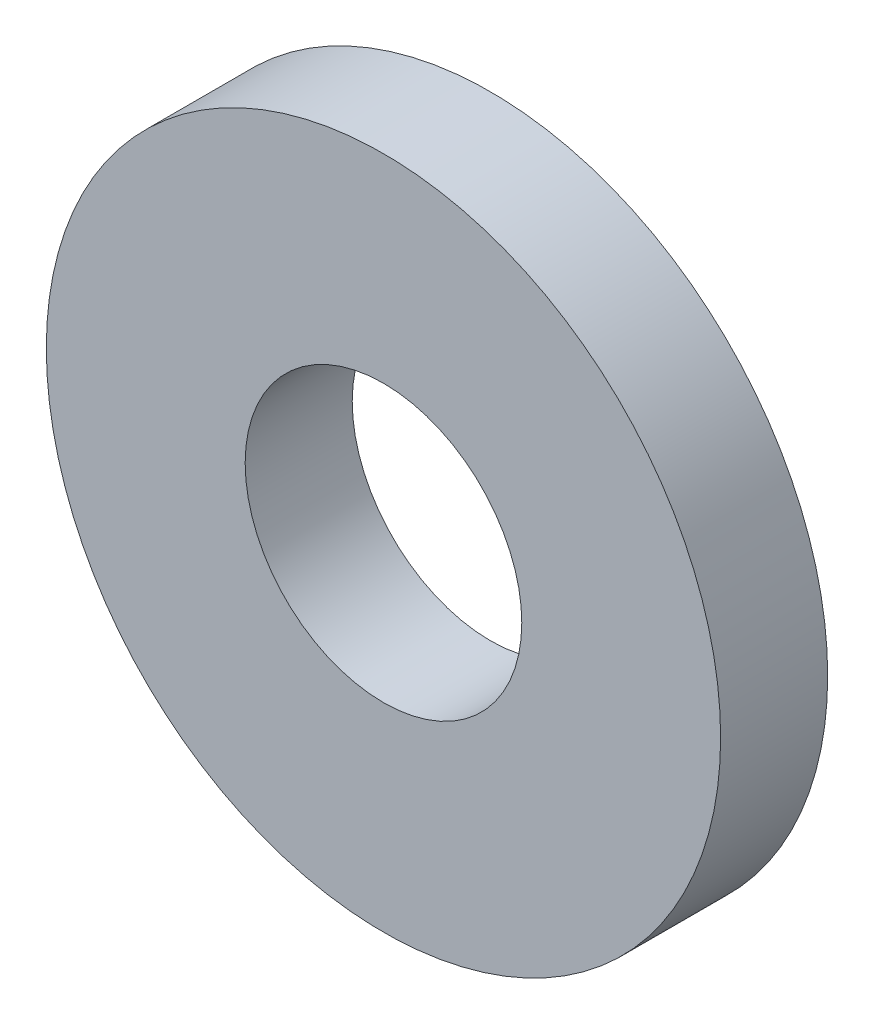
SolidWorks part; units mm, degrees
material "ABS"
ref_plane "Front Plane" through (0, 0, 0) normal (0, 0, 1) x (1, 0, 0)
ref_plane "Top Plane" through (0, 0, 0) normal (0, 1, 0) x (1, 0, 0)
ref_plane "Right Plane" through (0, 0, 0) normal (1, 0, 0) x (0, 0, -1)
sketch "Sketch1" plane through (0, 0, 0) normal (0, 0, 1) x (1, 0, 0)
  circle A0 centre (0, 0) radius 10
  dimension "D1" = 20
extrude "Boss-Extrude1" add sketch "Sketch1" along normal mid plane 3.175
hole_wizard "5/16 Clearance Hole1" positions "Sketch2" profile "Sketch3" hole size "5/16" standard "ANSI Inch" end condition through all
sketch "Sketch2" plane through (0, 0, 1.5875) normal (0, 0, 1) x (1, 0, 0)
  point P0 (0, 0)
sketch "Sketch3" plane through (0, 0, 1.5875) normal (1, 0, 0) x (0, -1, 0)
  line L0 (0, 0) -> (0, 3.175)
  line L1 (0, 3.175) -> (4.1021, 3.175)
  line L2 (4.1021, 3.175) -> (4.1021, 0)
  line L5 (4.1021, 0) -> (0, 0)
  line L11 (0, -6.35) -> (0, 107.95) construction
  dimension "Thru Hole Dia." = 8.2042
  dimension "Thru Hole Depth" = 3.175
equation "\"D1@Boss-Extrude1\"=0.125in"
